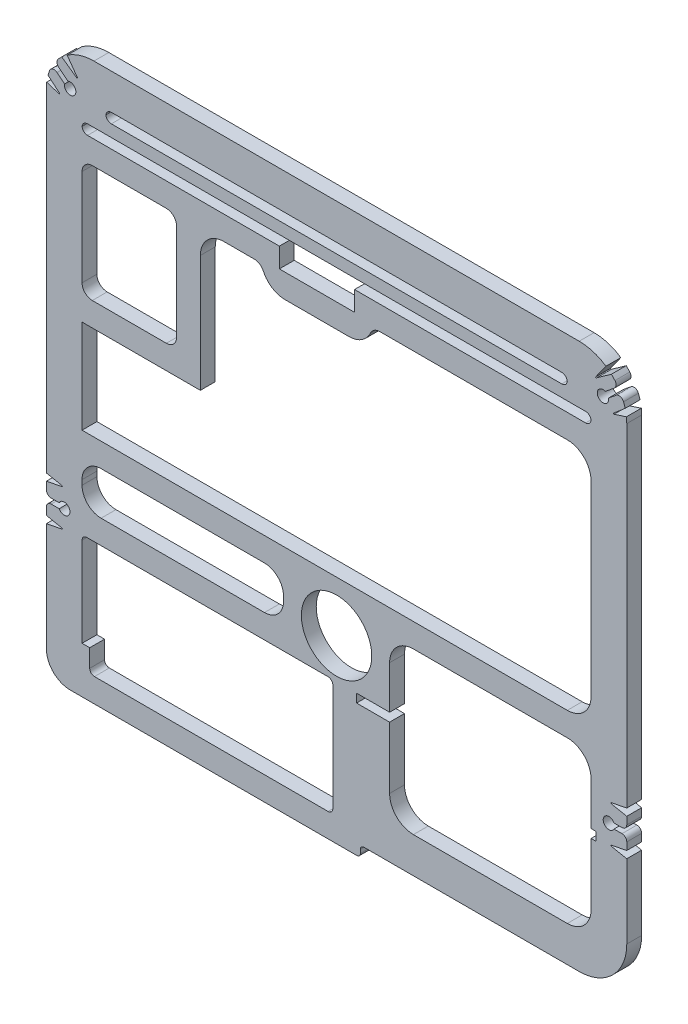
SolidWorks part; units mm, degrees
ref_plane "Front Plane" through (0, 0, 0) normal (0, 0, 1) x (1, 0, 0)
ref_plane "Top Plane" through (0, 0, 0) normal (0, 1, 0) x (1, 0, 0)
ref_plane "Right Plane" through (0, 0, 0) normal (1, 0, 0) x (0, 0, -1)
sketch "Sketch1" plane through (0, 0, 0) normal (0, 0, 1) x (1, 0, 0)
  line L0 (63.9883, 50.6392) -> (63.9883, 46.8292) construction
  line L1 (4.1102, -7.651) -> (66.0868, -7.651)
  line L2 (4.1102, -7.651) -> (4.1102, 50.6392)
  line L3 (4.1102, 50.6392) -> (66.0868, 50.6392)
  line L4 (66.0868, -7.651) -> (66.0868, 50.6392)
  line L5 (62.2768, 46.8292) -> (7.9202, 46.8292)
  line L6 (62.2768, 46.8292) -> (62.2768, -3.841)
  line L7 (62.2768, -3.841) -> (7.9202, -3.841)
  line L8 (7.9202, 46.8292) -> (7.9202, -3.841)
  line L9 (63.9883, 48.7342) -> (18.0707, 48.7342) construction
  line L10 (7.9202, 41.2855) -> (4.1102, 41.2855) construction
  line L11 (6.0152, 41.2855) -> (6.0152, 25.8577) construction
  line L12 (13.5248, -3.841) -> (13.5248, -7.651) construction
  line L13 (13.5248, -5.746) -> (21.1598, -5.746) construction
  line L14 (66.0868, 38.1916) -> (62.2768, 38.1916) construction
  line L15 (64.1818, 38.1916) -> (64.1818, 22.3321) construction
  line L16 (62.2768, 13.0613) -> (62.2768, 41.7492) construction
  line L17 (7.9202, 36.7962) -> (7.9202, 13.0613) construction
  line L22 (34.9556, 48.7342) -> (35.5018, 48.7342) construction
  line L23 (52.4244, -5.746) -> (51.8782, -5.746) construction
  dimension "D1" = 3.81
  dimension "D2" = 3.81
extrude "Boss-Extrude1" add sketch "Sketch1" along normal blind 1.5875
sketch "Sketch2" plane through (0, 0, 0) normal (0, 0, -1) x (-1, 0, 0)
  line L0 (-62.2768, -3.841) -> (-62.2768, 46.8292) construction
  line L1 (-62.2768, 15.868) -> (-7.9202, 15.868)
  line L2 (-62.2768, 15.868) -> (-62.2768, 13.328)
  line L3 (-62.2768, 13.328) -> (-7.9202, 13.328)
  line L4 (-7.9202, 15.868) -> (-7.9202, 13.328)
  line L5 (-7.9202, 46.8292) -> (-7.9202, -3.841) construction
  line L6 (-13.0532, 15.868) -> (-50.7532, 15.868) construction
  line L8 (-55.2788, 43.4256) -> (-16.9248, 43.4256) construction
  line L9 (-36.3812, 41.3174) -> (-29.6248, 41.3174) construction
  line L10 (-36.3812, 43.4256) -> (-36.3812, 41.3174) construction
  line L11 (-62.2768, 43.4256) -> (-37.0162, 43.4256)
  line L12 (-62.2768, 43.4256) -> (-62.2768, 40.8856)
  line L13 (-62.2768, 40.8856) -> (-38.9212, 40.8856)
  line L14 (-7.9202, 43.4256) -> (-7.9202, 40.8856)
  line L15 (-62.2768, 45.7624) -> (-7.9202, 45.7624)
  line L16 (-62.2768, 45.7624) -> (-62.2768, 44.4924)
  line L17 (-62.2768, 44.4924) -> (-7.9202, 44.4924)
  line L18 (-7.9202, 45.7624) -> (-7.9202, 44.4924)
  line L19 (-29.6248, 41.3174) -> (-29.6248, 43.4256) construction
  line L20 (-36.3812, 43.4256) -> (-36.3812, 41.3174) construction
  line L21 (-29.6248, 41.3174) -> (-29.6248, 43.4256) construction
  line L22 (-37.0162, 41.3174) -> (-37.0162, 43.4256)
  line L23 (-28.9898, 41.3174) -> (-37.0162, 41.3174)
  line L24 (-28.9898, 41.3174) -> (-28.9898, 43.4256)
  line L25 (-38.9212, 40.8856) -> (-38.9212, 38.7774)
  line L26 (-38.9212, 38.7774) -> (-27.0848, 38.7774)
  line L27 (-27.0848, 38.7774) -> (-27.0848, 40.8856)
  line L28 (-27.0848, 40.8856) -> (-7.9202, 40.8856)
  line L29 (-28.9898, 43.4256) -> (-7.9202, 43.4256)
  line L30 (-37.0162, 42.249) -> (-36.3812, 42.249) construction
  line L31 (-57.9086, 46.8292) -> (-57.9086, 45.7624) construction
  line L32 (-29.6248, 42.1673) -> (-28.9898, 42.1673) construction
  line L33 (-62.2768, 46.8292) -> (-7.9202, 46.8292) construction
  line L35 (-57.9086, 44.4924) -> (-57.9086, 43.4256) construction
  dimension "D1" = 2.54
  dimension "D2" = 1.905
  dimension "D3" = 2.54
  dimension "D4" = 1.905
  dimension "D5" = 1.27
  dimension "D6" = 0.635
extrude "Boss-Extrude2" add sketch "Sketch2" against normal up to surface (1.5875 mm away) up to face at (35.0985, 21.4941, 1.5875)
sketch "Sketch3" plane through (0, 0, 0) normal (0, 0, -1) x (-1, 0, 0)
  line L1 (-16.3032, 25.868) -> (-7.9202, 25.868) construction
  line L12 (-20.5532, 25.868) -> (-13.0532, 25.868)
  line L13 (-13.0532, 25.868) -> (-7.9202, 25.868)
  line L14 (-7.9202, 40.8856) -> (-7.9202, 15.868) construction
  line L15 (-7.9202, 25.868) -> (-7.9202, 28.408)
  line L16 (-7.9202, 28.408) -> (-18.0132, 28.408)
  line L17 (-18.0132, 28.408) -> (-18.0132, 40.8856)
  line L18 (-27.0848, 40.8856) -> (-7.9202, 40.8856) construction
  line L19 (-18.0132, 40.8856) -> (-20.5532, 40.8856)
  line L20 (-20.5532, 40.8856) -> (-20.5532, 25.868)
  line M27 (-27.0848, 40.8856) -> (-7.9202, 40.8856)
  line M28 (-7.9202, 40.8856) -> (-7.9202, 15.868)
  dimension "D3" = 2.54
  dimension "D4" = 2.54
extrude "Boss-Extrude3" add sketch "Sketch3" against normal up to surface (1.5875 mm away) contours L20 L12 L13 L16 L17 M27 M28 region at (20.3569, 33.3768, 0) up to face at (35.0985, 46.2958, 1.5875)
sketch "Sketch4" plane through (0, 0, 0) normal (0, 0, -1) x (-1, 0, 0)
  line L0 (-62.2768, 13.328) -> (-7.9202, 13.328) construction
  line L1 (-40.7627, 13.328) -> (-29.4343, 13.328)
  line L2 (-40.7627, 13.328) -> (-40.7627, -3.841)
  line L3 (-40.7627, -3.841) -> (-29.4343, -3.841)
  line L4 (-29.4343, 13.328) -> (-29.4343, -3.841)
  line L5 (-7.9202, -3.841) -> (-62.2768, -3.841) construction
  line L6 (-38.8577, 10.4578) -> (-40.7627, 10.4578) construction
  line L7 (-31.3393, 10.4578) -> (-29.4343, 10.4578) construction
  dimension "D1" = 1.905
extrude "Boss-Extrude4" add sketch "Sketch4" against normal up to surface (1.5875 mm away) up to face at (12.9667, 34.6468, 1.5875)
sketch "Sketch5" plane through (0, 0, 0) normal (0, 0, -1) x (-1, 0, 0)
  line L1 (-8.7364, -6.254) -> (-34.6952, -6.254) construction
  line L2 (-8.7364, -6.254) -> (-8.7364, 6.2047) construction
  line L6 (-8.7364, 6.2047) -> (-34.6952, 6.2047) construction
  line L7 (-34.6952, -6.254) -> (-34.6952, 6.2047) construction
  line L8 (-8.7364, -6.254) -> (-34.6952, -6.254)
  line L9 (-8.7364, -6.254) -> (-8.7364, 6.2047)
  line L10 (-8.7364, 6.2047) -> (-34.6952, 6.2047)
  line L11 (-34.6952, -6.254) -> (-34.6952, 6.2047)
  circle A1 centre (-35.0985, 10.4578) radius 3.7592 construction
  circle A2 centre (-35.0985, 10.4578) radius 3.7592
extrude "Cut-Extrude1" cut sketch "Sketch5" against normal up to surface (1.5875 mm away) up to face at (51.5197, 4.7435, 1.5875)
sketch "Sketch10" plane through (0, 0, 1.5875) normal (0, 0, 1) x (1, 0, 0)
  line L0 (29.4343, 13.328) -> (29.4343, 6.2047) construction
  line L1 (7.9202, 6.2047) -> (29.4343, 6.2047)
  line L2 (7.9202, 6.2047) -> (7.9202, 8.7447)
  line L3 (7.9202, 8.7447) -> (29.4343, 8.7447)
  line L4 (29.4343, 6.2047) -> (29.4343, 8.7447)
  line L5 (7.9202, 13.328) -> (7.9202, -3.841) construction
  line L6 (34.6952, 6.2047) -> (29.4343, 6.2047) construction
  dimension "D1" = 2.54
extrude "Boss-Extrude5" add sketch "Sketch10" against normal up to surface (1.5875 mm away) up to face at (20.1965, 2.3595, 0)
fillet "Fillet1" radius 5.08 3 edges at (66.0868, -7.651, 0.7937) (4.1102, 50.6392, 0.7937) (66.0868, 50.6392, 0.7937)
fillet "Fillet2" radius 2.54 5 edges at (20.5532, 40.8856, 0.7937) (27.0848, 38.7774, 0.7937) (62.2768, 40.8856, 0.7937) (62.2768, 15.868, 0.7937) (38.9212, 38.7774, 0.7937)
fillet "Fillet3" radius 1.0922 6 edges at (7.9202, 28.408, 0.7937) (18.0132, 28.408, 0.7937) (7.9202, 40.8856, 0.7937) (18.0132, 40.8856, 0.7937) (27.0848, 40.8856, 0.7937) (38.9212, 40.8856, 0.7937)
fillet "Fillet4" radius 0.5842 4 edges at (7.9202, 43.4256, 0.7937) (7.9202, 44.4924, 0.7937) (62.2768, 44.4924, 0.7937) (62.2768, 43.4256, 0.7937)
sketch "Sketch6" plane through (0, 0, 0) normal (0, 0, -1) x (-1, 0, 0)
  line L0 (-9.5532, 24.368) -> (-9.5532, 17.368) construction
  line L1 (-9.5532, 24.368) -> (-9.5532, 17.368)
  line L2 (-11.0532, 25.868) -> (-9.5532, 24.368) construction
  line L3 (-11.0532, 25.868) -> (-9.5532, 24.368)
  line L4 (-11.0532, 25.868) -> (-11.0532, 15.868)
  line L6 (-13.0532, 17.368) -> (-13.0532, 15.868)
  line L7 (-13.0532, 15.868) -> (-11.0532, 15.868)
  line L8 (-11.0532, 15.868) -> (-9.5532, 17.368)
  line L9 (-9.5532, 17.368) -> (-13.0532, 17.368)
  line L12 (-11.0532, 15.868) -> (-9.5532, 17.368)
  circle A0 centre (-63.5468, 46.8292) radius 0.6096 construction
  circle A1 centre (-6.6502, 46.8292) radius 0.6096 construction
  circle A2 centre (-64.1818, 7.6638) radius 0.6096 construction
  circle A3 centre (-6.0152, 7.6638) radius 0.6096 construction
  circle A4 centre (-63.5468, 46.8292) radius 0.6096
  circle A5 centre (-6.6502, 46.8292) radius 0.6096
  circle A6 centre (-64.1818, 7.6638) radius 0.6096
  circle A7 centre (-6.0152, 7.6638) radius 0.6096
  dimension "D1" = 0
extrude "Cut-Extrude2" cut sketch "Sketch6" against normal up to surface (1.5875 mm away) up to face at (17.1172, -1.2967, 1.5875)
sketch "Sketch9" plane through (0, 0, 1.5875) normal (0, 0, 1) x (1, 0, 0)
  line L4 (62.813, 6.2047) -> (37.2352, 6.2047)
  line L5 (37.2352, 6.2047) -> (37.2352, 5.2903)
  line L6 (37.2352, 5.2903) -> (62.813, 5.2903)
  line L7 (62.813, 5.2903) -> (62.813, 6.2047)
  line L8 (62.813, 6.2047) -> (37.2352, 6.2047)
  line L9 (37.2352, 6.2047) -> (37.2352, 5.2903)
  line L10 (37.2352, 5.2903) -> (62.813, 5.2903)
  line L11 (62.813, 5.2903) -> (62.813, 6.2047)
  dimension "D1" = 0
extrude "Cut-Extrude3" cut sketch "Sketch9" against normal up to surface (1.5875 mm away) up to face at (5.4056, 7.6638, 0)
fillet "Fillet6" radius 0.508 4 edges at (34.6952, 6.2047, 0.7937) (34.6952, -6.254, 0.7937) (8.7364, -6.254, 0.7937) (7.9202, 6.2047, 0.7937)
sketch "Sketch11" plane through (0, 0, 1.5875) normal (0, 0, 1) x (1, 0, 0)
  line L0 (9.2444, -6.254) -> (34.1872, -6.254) construction
  line L1 (4.1102, -7.651) -> (37.6385, -7.651)
  line L2 (4.1102, -7.651) -> (4.1102, -8.794)
  line L3 (4.1102, -8.794) -> (37.6385, -8.794)
  line L4 (37.6385, -7.651) -> (37.6385, -8.794)
  line L5 (35.0985, 14.217) -> (35.0985, -22.2214) construction
  circle A0 centre (35.0985, 10.4578) radius 3.7592 construction
  dimension "D1" = 2.54
  dimension "D2" = 2.54
extrude "Boss-Extrude6" add sketch "Sketch11" against normal up to surface (1.5875 mm away) up to face at (51.0212, 5.4129, 0)
fillet "Fillet7" radius 2.54 1 edges at (4.1102, -8.794, 0.7937)
fillet "Fillet8" radius 0.381 2 edges at (37.6385, -8.794, 0.7937) (37.6385, -7.651, 0.7937)
fillet "Fillet9" radius 2.032 4 edges at (29.4343, 8.7447, 0.7937) (29.4343, 13.328, 0.7937) (7.9202, 8.7447, 0.7937) (7.9202, 13.328, 0.7937)
fillet "Fillet10" radius 2.54 4 edges at (40.7627, -3.841, 0.7937) (62.2768, -3.841, 0.7937) (62.2768, 13.328, 0.7937) (40.7627, 13.328, 0.7937)
sketch "Sketch12" plane through (0, 0, 1.5875) normal (0, 0, 1) x (1, 0, 0)
  line L0 (7.9202, 46.8292) -> (7.9202, 45.7624) construction
  line L1 (7.9202, 46.8292) -> (10.4602, 46.8292)
  line L2 (7.9202, 46.8292) -> (7.9202, 45.7624)
  line L3 (7.9202, 45.7624) -> (10.4602, 45.7624)
  line L4 (10.4602, 46.8292) -> (10.4602, 45.7624)
  line L5 (62.2768, 46.8292) -> (7.9202, 46.8292) construction
  line L6 (62.2768, 45.7624) -> (7.9202, 45.7624) construction
  line L8 (62.2768, 46.8292) -> (59.7368, 46.8292)
  line L9 (62.2768, 46.8292) -> (62.2768, 45.7624)
  line L10 (62.2768, 45.7624) -> (59.7368, 45.7624)
  line L11 (59.7368, 46.8292) -> (59.7368, 45.7624)
  dimension "D1" = 2.54
extrude "Boss-Extrude7" add sketch "Sketch12" against normal up to surface (1.5875 mm away) up to face at (51.1458, 5.2455, 0)
fillet "Fillet11" radius 0.5842 4 edges at (59.7368, 45.7624, 0.7937) (59.7368, 46.8292, 0.7937) (10.4602, 45.7624, 0.7937) (10.4602, 46.8292, 0.7937)
sketch "Sketch13" plane through (0, 0, 1.5875) normal (0, 0, 1) x (1, 0, 0)
  line L0 (4.1471, 46.1706) -> (5.4628, 45.7479) construction
  line L1 (5.5112, 45.8349) -> (4.2848, 46.8798) construction
  line L2 (5.2504, 47.6106) -> (6.0537, 46.9553) construction
  line L3 (6.407, 47.3882) -> (5.4336, 48.1824) construction
  line L4 (5.7558, 49.3025) -> (7.3477, 48.1654) construction
  line L5 (7.4186, 48.2363) -> (6.3313, 49.7585) construction
  line L6 (6.6502, -8.794) -> (37.2575, -8.794)
  line L7 (37.6385, -8.413) -> (37.6385, -8.032)
  line L8 (38.0195, -7.651) -> (61.0068, -7.651)
  line L9 (66.0868, -2.571) -> (66.0868, 45.5592)
  line L10 (61.0068, 50.6392) -> (9.1902, 50.6392)
  line L11 (4.1102, 45.5592) -> (4.1102, -6.254)
  line L15 (66.0868, 5.3189) -> (66.0868, 6.0809)
  line L17 (4.1102, 10.0088) -> (4.1102, 9.2468)
  line L18 (4.1471, 46.1706) -> (5.4628, 45.7479)
  line L19 (5.5112, 45.8349) -> (4.2848, 46.8798)
  line L20 (5.2504, 47.6106) -> (6.0537, 46.9553)
  line L21 (6.407, 47.3882) -> (5.4336, 48.1824)
  line L22 (5.7558, 49.3025) -> (7.3477, 48.1654)
  line L23 (7.4186, 48.2363) -> (6.3313, 49.7585)
  line L24 (5.7661, 9.6776) -> (4.1102, 10.0088) construction
  line L25 (4.1102, 9.2468) -> (5.7661, 9.578) construction
  line L26 (5.4734, 7.9432) -> (4.6182, 7.9432) construction
  line L27 (4.6182, 7.3844) -> (5.4734, 7.3844) construction
  line L28 (5.7661, 5.7497) -> (4.1102, 6.0809) construction
  line L29 (4.1102, 5.3189) -> (5.7661, 5.6501) construction
  line L30 (5.7661, 9.6776) -> (4.1102, 10.0088)
  line L31 (4.1102, 9.2468) -> (5.7661, 9.578)
  line L32 (5.4734, 7.9432) -> (4.6182, 7.9432)
  line L33 (4.6182, 7.3844) -> (5.4734, 7.3844)
  line L34 (5.7661, 5.7497) -> (4.1102, 6.0809)
  line L35 (4.1102, 5.3189) -> (5.7661, 5.6501)
  line L36 (66.0868, 5.3189) -> (64.4308, 5.6501) construction
  line L37 (64.4308, 5.7497) -> (66.0868, 6.0809) construction
  line L38 (65.5788, 7.3844) -> (64.7236, 7.3844) construction
  line L39 (64.7236, 7.9432) -> (65.5788, 7.9432) construction
  line L40 (66.0868, 9.2468) -> (64.4308, 9.578) construction
  line L41 (64.4308, 9.6776) -> (66.0868, 10.0088) construction
  line L42 (66.0868, 5.3189) -> (64.4308, 5.6501)
  line L43 (64.4308, 5.7497) -> (66.0868, 6.0809)
  line L44 (65.5788, 7.3844) -> (64.7236, 7.3844)
  line L45 (64.7236, 7.9432) -> (65.5788, 7.9432)
  line L46 (66.0868, 9.2468) -> (64.4308, 9.578)
  line L47 (64.4308, 9.6776) -> (66.0868, 10.0088)
  line L48 (62.7783, 48.2363) -> (63.8656, 49.7585) construction
  line L49 (64.4411, 49.3025) -> (62.8492, 48.1654) construction
  line L50 (63.79, 47.3882) -> (64.7634, 48.1824) construction
  line L51 (64.9465, 47.6106) -> (64.1432, 46.9553) construction
  line L52 (64.6857, 45.8349) -> (65.9121, 46.8798) construction
  line L53 (66.0498, 46.1706) -> (64.7342, 45.7479) construction
  line L54 (62.7783, 48.2363) -> (63.8656, 49.7585)
  line L55 (64.4411, 49.3025) -> (62.8492, 48.1654)
  line L56 (63.79, 47.3882) -> (64.7634, 48.1824)
  line L57 (64.9465, 47.6106) -> (64.1432, 46.9553)
  line L58 (64.6857, 45.8349) -> (65.9121, 46.8798)
  line L59 (66.0498, 46.1706) -> (64.7342, 45.7479)
  line L60 (66.0868, -2.571) -> (66.0868, 45.5592) construction
  line L61 (66.0868, 5.3189) -> (66.0868, 10.0088)
  line L62 (66.0868, 9.2468) -> (66.0868, 10.0088)
  line L63 (66.0868, 6.8764) -> (66.0868, 8.4512)
  line L64 (4.1102, 45.5592) -> (4.1102, -6.254) construction
  line L65 (4.1102, 10.0088) -> (4.1102, 9.2468)
  line L66 (4.1102, 6.0809) -> (4.1102, 5.3189)
  line L67 (4.1102, 8.4512) -> (4.1102, 6.8764)
  line L68 (4.1102, 8.4512) -> (4.1102, 5.3189)
  arc A0 (5.4628, 45.7479) -> (5.5112, 45.8349) centre (5.4783, 45.7963) ccw construction
  arc A1 (5.2504, 47.6106) -> (4.4559, 47.4012) centre (4.9293, 47.217) ccw construction
  arc A2 (5.373, 48.9112) -> (5.4336, 48.1824) centre (5.7547, 48.576) ccw construction
  arc A3 (7.3477, 48.1654) -> (7.4186, 48.2363) centre (7.3772, 48.2068) ccw construction
  arc A4 (5.4628, 45.7479) -> (5.5112, 45.8349) centre (5.4783, 45.7963) ccw
  arc A5 (5.2504, 47.6106) -> (4.4559, 47.4012) centre (4.9293, 47.217) ccw
  arc A6 (37.2575, -8.794) -> (37.6385, -8.413) centre (37.2575, -8.413) ccw
  arc A7 (38.0195, -7.651) -> (37.6385, -8.032) centre (38.0195, -8.032) ccw
  arc A8 (61.0068, -7.651) -> (66.0868, -2.571) centre (61.0068, -2.571) ccw
  arc A9 (66.0868, 45.5592) -> (61.0068, 50.6392) centre (61.0068, 45.5592) ccw
  arc A10 (9.1902, 50.6392) -> (4.1102, 45.5592) centre (9.1902, 45.5592) ccw
  arc A11 (4.1102, -6.254) -> (6.6502, -8.794) centre (6.6502, -6.254) ccw
  arc A15 (66.0498, 46.1706) -> (65.9121, 46.8798) centre (61.0068, 45.5592) ccw
  arc A16 (6.3313, 49.7585) -> (5.7558, 49.3025) centre (9.1902, 45.5592) ccw
  arc A18 (5.373, 48.9112) -> (5.4336, 48.1824) centre (5.7547, 48.576) ccw
  arc A19 (7.3477, 48.1654) -> (7.4186, 48.2363) centre (7.3772, 48.2068) ccw
  arc A20 (5.7661, 9.578) -> (5.7661, 9.6776) centre (5.7561, 9.6278) ccw construction
  arc A21 (4.1102, 8.4512) -> (4.6182, 7.9432) centre (4.6182, 8.4512) ccw construction
  arc A22 (4.6182, 7.3844) -> (4.1102, 6.8764) centre (4.6182, 6.8764) ccw construction
  arc A23 (5.7661, 5.6501) -> (5.7661, 5.7497) centre (5.7561, 5.6999) ccw construction
  arc A24 (5.7661, 9.578) -> (5.7661, 9.6776) centre (5.7561, 9.6278) ccw
  arc A25 (4.1102, 8.4512) -> (4.6182, 7.9432) centre (4.6182, 8.4512) ccw
  arc A26 (4.6182, 7.3844) -> (4.1102, 6.8764) centre (4.6182, 6.8764) ccw
  arc A27 (5.7661, 5.6501) -> (5.7661, 5.7497) centre (5.7561, 5.6999) ccw
  arc A28 (64.4308, 5.7497) -> (64.4308, 5.6501) centre (64.4408, 5.6999) ccw construction
  arc A29 (66.0868, 6.8764) -> (65.5788, 7.3844) centre (65.5788, 6.8764) ccw construction
  arc A30 (65.5788, 7.9432) -> (66.0868, 8.4512) centre (65.5788, 8.4512) ccw construction
  arc A31 (64.4308, 9.6776) -> (64.4308, 9.578) centre (64.4408, 9.6278) ccw construction
  arc A32 (64.4308, 5.7497) -> (64.4308, 5.6501) centre (64.4408, 5.6999) ccw
  arc A33 (66.0868, 6.8764) -> (65.5788, 7.3844) centre (65.5788, 6.8764) ccw
  arc A34 (65.5788, 7.9432) -> (66.0868, 8.4512) centre (65.5788, 8.4512) ccw
  arc A35 (64.4308, 9.6776) -> (64.4308, 9.578) centre (64.4408, 9.6278) ccw
  arc A36 (62.7783, 48.2363) -> (62.8492, 48.1654) centre (62.8197, 48.2068) ccw construction
  arc A37 (64.7634, 48.1824) -> (64.8239, 48.9112) centre (64.4422, 48.576) ccw construction
  arc A38 (65.7411, 47.4012) -> (64.9465, 47.6106) centre (65.2676, 47.217) ccw construction
  arc A39 (64.6857, 45.8349) -> (64.7342, 45.7479) centre (64.7186, 45.7963) ccw construction
  arc A40 (62.7783, 48.2363) -> (62.8492, 48.1654) centre (62.8197, 48.2068) ccw
  arc A41 (64.7634, 48.1824) -> (64.8239, 48.9112) centre (64.4422, 48.576) ccw
  arc A42 (65.7411, 47.4012) -> (64.9465, 47.6106) centre (65.2676, 47.217) ccw
  arc A43 (64.6857, 45.8349) -> (64.7342, 45.7479) centre (64.7186, 45.7963) ccw
  arc A44 (66.0868, 45.5592) -> (61.0068, 50.6392) centre (61.0068, 45.5592) ccw construction
  circle A45 centre (63.5468, 46.8292) radius 0.6096 construction
  arc A46 (66.0498, 46.1706) -> (63.8656, 49.7585) centre (61.0068, 45.5592) ccw
  arc A47 (64.1432, 46.9553) -> (63.79, 47.3882) centre (63.5468, 46.8292) ccw
  arc A48 (64.4411, 49.3025) -> (63.8656, 49.7585) centre (61.0068, 45.5592) ccw
  arc A49 (65.7411, 47.4012) -> (64.8239, 48.9112) centre (61.0068, 45.5592) ccw
  circle A50 centre (64.1818, 7.6638) radius 0.6096 construction
  arc A51 (64.7236, 7.3844) -> (64.7236, 7.9432) centre (64.1818, 7.6638) ccw
  circle A52 centre (6.0152, 7.6638) radius 0.6096 construction
  arc A53 (5.4734, 7.9432) -> (5.4734, 7.3844) centre (6.0152, 7.6638) ccw
  arc A54 (5.373, 48.9112) -> (4.4559, 47.4012) centre (9.1902, 45.5592) ccw
  arc A55 (4.2848, 46.8798) -> (4.1471, 46.1706) centre (9.1902, 45.5592) ccw
  circle A56 centre (6.6502, 46.8292) radius 0.6096 construction
  arc A57 (6.407, 47.3882) -> (6.0537, 46.9553) centre (6.6502, 46.8292) ccw
  dimension "D1" = 0
extrude "Cut-Extrude4" cut sketch "Sketch13" against normal through all contours L22 A19 L23 A16 | A57 L21 A18 A54 A5 L20 | L19 A55 L18 A4 | L35 A27 L34 L66 | A53 L32 A25 L67 A26 L33 | L31 A24 L30 L17 | L43 A32 L42 L15 | A51 L44 A33 L61 A34 L45 | L47 A35 L46 L61 | L55 A46 L54 A40 | A47 L57 A42 A46 A41 L56 | L58 A43 L59 A15 region at (4.7305, 5.6999, 1.5875) region at (4.6977, 7.6638, 1.5875) region at (4.7305, 9.6278, 1.5875) region at (65.4665, 5.6999, 1.5875) region at (65.4992, 7.6638, 1.5875) region at (4.6929, 46.2513, 1.5875) region at (65.4665, 9.6278, 1.5875) region at (5.458, 47.7782, 1.5875) region at (6.5431, 49.0342, 1.5875) region at (65.504, 46.2513, 1.5875) region at (64.7389, 47.7782, 1.5875) region at (63.6538, 49.0342, 1.5875)
